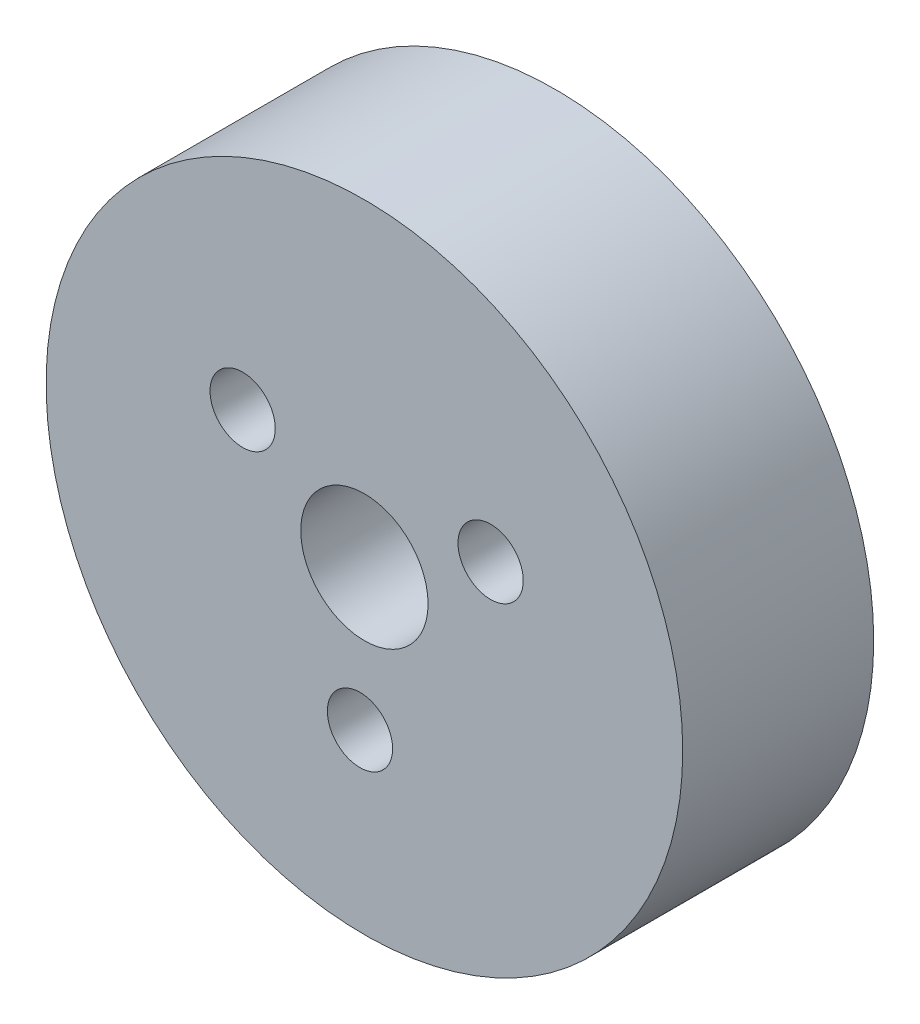
SolidWorks part; units mm, degrees
ref_plane "Front Plane" through (0, 0, 0) normal (0, 0, 1) x (1, 0, 0)
ref_plane "Top Plane" through (0, 0, 0) normal (0, 1, 0) x (1, 0, 0)
ref_plane "Right Plane" through (0, 0, 0) normal (1, 0, 0) x (0, 0, -1)
sketch "Sketch1" plane through (0, 0, 0) normal (0, 0, 1) x (1, 0, 0)
  circle A0 centre (0, 0) radius 10
  circle A1 centre (0, 0) radius 2
  dimension "D1" = 4
  dimension "D2" = 20
extrude "Boss-Extrude1" add sketch "Sketch1" along normal blind 6
hole_wizard "Ø2.05 (2.05) Diameter Hole1" positions "Sketch2" profile "Sketch3" hole size "Ø2.05" standard "ISO" end condition through all
sketch "Sketch2" plane through (-167.3405, 18.1878, 6.7366) normal (0, 0, 1) x (0.0586, -0.9983, 0)
  circle A0 centre (27.9652, 165.9867) radius 4.5
  point P0 (32.4472, 165.5842)
  point P2 (25.3756, 162.3065)
  point P4 (26.0728, 170.0695)
sketch "Sketch3" plane through (-0.1391, -4.4978, 6.7366) normal (1, 0, 0) x (0, -1, 0)
  line L0 (0, 0) -> (0, 6.7366)
  line L1 (0, 6.7366) -> (1.025, 6.7366)
  line L2 (1.025, 6.7366) -> (1.025, 0)
  line L3 (1.025, 0) -> (0, 0)
  line L4 (0, -6.35) -> (0, 107.95) construction
  dimension "Thru Hole Dia." = 2.05
  dimension "Thru Hole Depth" = 6.7366
